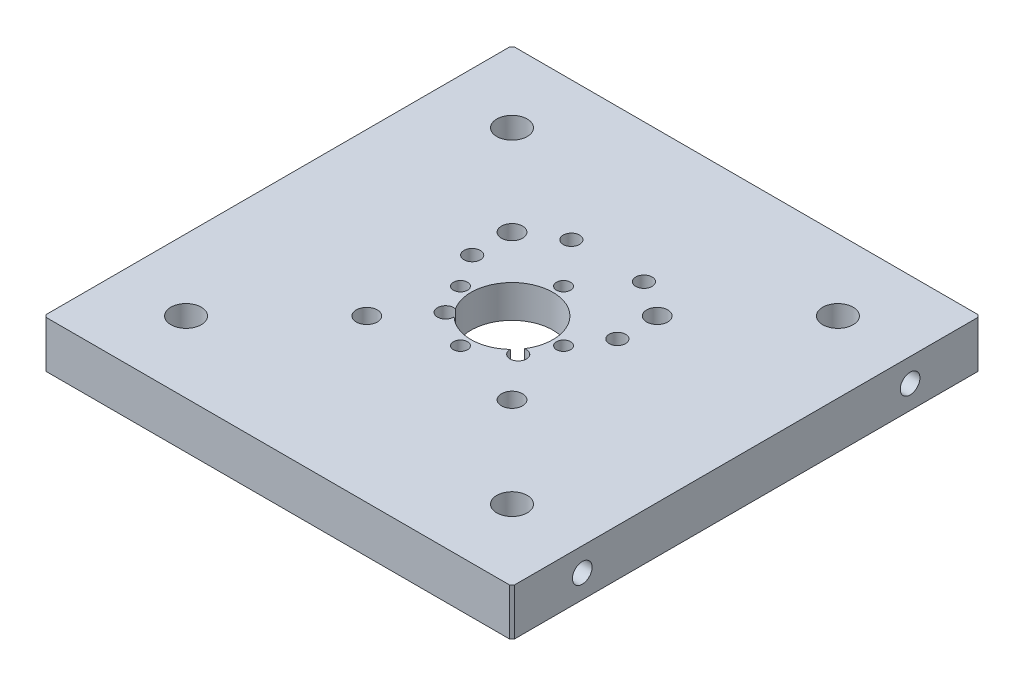
SolidWorks part; units mm, degrees
material "6061 Alloy"
ref_plane "Front Plane" through (0, 0, 0) normal (0, 0, 1) x (1, 0, 0)
ref_plane "Top Plane" through (0, 0, 0) normal (0, 1, 0) x (1, 0, 0)
ref_plane "Right Plane" through (0, 0, 0) normal (1, 0, 0) x (0, 0, -1)
sketch "Sketch1" plane through (0, 0, 0) normal (0, 1, 0) x (1, 0, 0)
  line L0 (0, 50) -> (0, -50) construction
  line L1 (-50, 50) -> (50, 50)
  line L2 (-50, 50) -> (-50, -50)
  line L3 (-50, -50) -> (50, -50)
  line L4 (50, 50) -> (50, -50)
  line L5 (-50, 0) -> (50, 0) construction
  point P8 (0, 0)
  dimension "D1" = 100
  dimension "D2" = 0
extrude "Boss-Extrude1" add sketch "Sketch1" along normal blind 5 and the other way blind 5
sketch "Sketch2" plane through (0, 5, 0) normal (0, 1, 0) x (1, 0, 0)
  line L1 (0, 50) -> (0, -50) construction
  line L2 (50, 50) -> (-50, 50) construction
  line L3 (-50, -50) -> (50, -50) construction
  line L4 (-50, 0) -> (50, 0) construction
  line L5 (-50, 50) -> (-50, -50) construction
  line L6 (50, -50) -> (50, 50) construction
  circle A0 centre (0, 0) radius 8.75
  circle A1 centre (-34.7985, 34.7985) radius 3.25
  circle A2 centre (34.7985, 34.7985) radius 3.25
  circle A3 centre (34.7985, -34.7985) radius 3.25
  circle A4 centre (-34.7985, -34.7985) radius 3.25
  dimension "D1" = 6.5
  dimension "D3" = 17.5
  dimension "D2" = 34.7985
  dimension "D4" = 34.7985
  dimension "D5" = 34.7985
  dimension "D6" = 50
  dimension "D7" = 50
extrude "Cut-Extrude1" cut sketch "Sketch2" against normal blind 12.7
hole_wizard "Tap Drill for M5x0.8 Tap1" positions "Sketch9" profile "Sketch10" hole size "M5x0.8" standard "ANSI Metric"
sketch "Sketch9" plane through (-50, 0, 0) normal (-1, 0, 0) x (0, 0, 1)
  line L0 (-50, -5) -> (50, -5) construction
  line L1 (-50, 5) -> (-50, -5) construction
  line L2 (50, 5) -> (50, -5) construction
  point P0 (-35, 0)
  point P2 (35, 0)
  dimension "D1" = 5
  dimension "D2" = 15
  dimension "D3" = 5
  dimension "D4" = 15
sketch "Sketch10" plane through (-50, 0, -35) normal (0, 1, 0) x (0, 0, 1)
  line L0 (0, 0) -> (0, 11.2618)
  line L1 (0, 11.2618) -> (2.1, 10)
  line L2 (2.1, 10) -> (2.1, 0)
  line L5 (2.1, 0) -> (0, 0)
  line L10 (0, 11.2618) -> (-2.1, 10) construction
  line L11 (0, -6.35) -> (0, 107.95) construction
  dimension "Hole Dia." = 4.2
  dimension "Hole Depth" = 10
  dimension "Drill Angle" = 118
sketch "Sketch11" plane through (0, -5, 0) normal (0, -1, 0) x (1, 0, 0)
  circle A0 centre (0, 0) radius 37.5
  dimension "D1" = 75
extrude "Cut-Extrude2" cut sketch "Sketch11" against normal blind 3
chamfer "Chamfer1" distance 0.5 angle 45 4 edges at (50, 0, -50) (50, 0, 50) (-50, 0, 50) (-50, 0, -50)
ref_plane "Plane1" through (0, 0, 0) normal (-1, 0, 0) x (0, 0, 1)
mirror "Mirror1" about plane through (0, 0, 0) normal (-1, 0, 0) of "Tap Drill for M5x0.8 Tap1"
sketch "Sketch12" plane through (0, 5, 0) normal (0, 1, 0) x (1, 0, 0)
  line L0 (0, 50) -> (0, -50) construction
  circle A0 centre (-15.5, 7) radius 1.75
  circle A1 centre (15.5, 7) radius 1.75
  circle A3 centre (-7.75, 20.4234) radius 1.75
  circle A4 centre (7.75, 20.4234) radius 1.75
  circle A5 centre (15.5, 7) radius 1.75
  circle A6 centre (7.75, -6.4234) radius 1.75
  circle A7 centre (-7.75, -6.4234) radius 1.75
  point P23 (0, 7)
  dimension "D1" = 7
  dimension "D3" = 6
  dimension "D4" = 3.5
  dimension "D2" = 15.5
extrude "Cut-Extrude3" cut sketch "Sketch12" against normal through all contours A4 | A3 | A1 | A6 | A7 | A0 region at (7.75, 5, -20.4234)
sketch "Sketch13" plane through (0, 5, 0) normal (0, 1, 0) x (1, 0, 0)
  circle A0 centre (0, 0) radius 21.9203
  circle A1 centre (-15.5, -15.5) radius 2.25
  circle A2 centre (-15.5, 15.5) radius 2.25
  circle A3 centre (15.5, 15.5) radius 2.25
  circle A4 centre (15.5, -15.5) radius 2.25
  point P13 (0, 0)
  dimension "D1" = 15.5
  dimension "D4" = 4.5
  dimension "D2" = 15.5
  dimension "D3" = 4
extrude "Cut-Extrude4" cut sketch "Sketch13" against normal blind 10 contours A2 | A3 | A4 | A1
sketch "Sketch14" plane through (0, 5, 0) normal (0, 1, 0) x (1, 0, 0)
  line L0 (0, 50) -> (0, -50) construction
  line L1 (-50, 0) -> (50, 0) construction
  circle A0 centre (0, 11) radius 1.5
  circle A1 centre (-11, 0) radius 1.5
  circle A2 centre (0, -11) radius 1.5
  circle A3 centre (11, 0) radius 1.5
  dimension "D1" = 11
  dimension "D2" = 11
  dimension "D3" = 11
  dimension "D4" = 11
extrude "Cut-Extrude5" cut sketch "Sketch14" against normal blind 10
